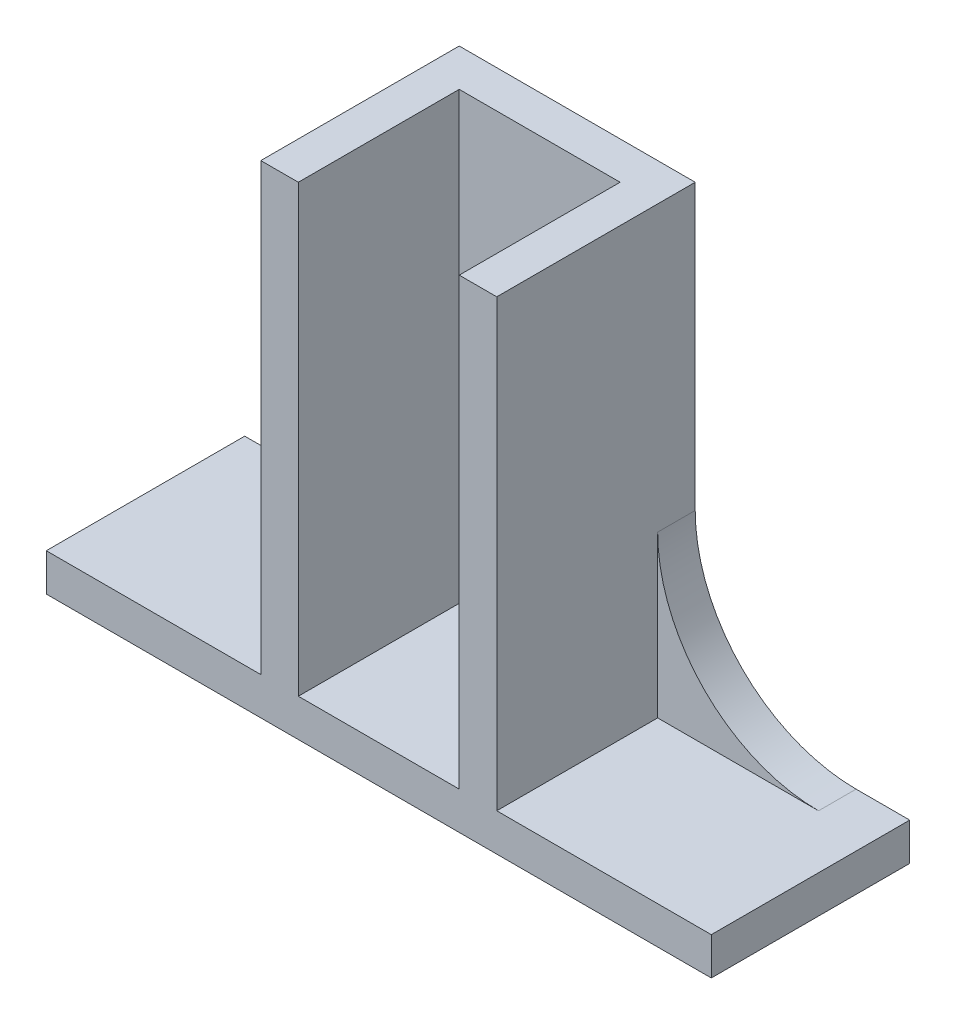
SolidWorks part; units mm, degrees
ref_plane "Front Plane" through (0, 0, 0) normal (0, 0, 1) x (1, 0, 0)
ref_plane "Top Plane" through (0, 0, 0) normal (0, 1, 0) x (1, 0, 0)
ref_plane "Right Plane" through (0, 0, 0) normal (1, 0, 0) x (0, 0, -1)
sketch "Sketch1" plane through (0, 0, 0) normal (0, 0, 1) x (1, 0, 0)
  line L1 (-16.1393, 44.8689) -> (5.8607, 44.8689)
  line L2 (-16.1393, 44.8689) -> (-16.1393, -0.1311)
  line L3 (-16.1393, -0.1311) -> (5.8607, -0.1311)
  line L4 (5.8607, 44.8689) -> (5.8607, -0.1311)
  dimension "D1" = 22
  dimension "D2" = 45
extrude "Boss-Extrude1" add sketch "Sketch1" along normal blind 18.5
sketch "Sketch2" plane through (0, 0, 18.5) normal (0, 0, 1) x (1, 0, 0)
  line L0 (5.8607, 44.8689) -> (-16.1393, 44.8689) construction
  line L1 (-12.6393, 44.8689) -> (2.3607, 44.8689)
  line L2 (-12.6393, 44.8689) -> (-12.6393, 3.3689)
  line L3 (-12.6393, 3.3689) -> (2.3607, 3.3689)
  line L4 (2.3607, 44.8689) -> (2.3607, 3.3689)
  line L5 (5.8607, -0.1311) -> (5.8607, 44.8689) construction
  line L6 (-16.1393, -0.1311) -> (5.8607, -0.1311) construction
  dimension "D1" = 15
  dimension "D2" = 3.5
  dimension "D3" = 3.5
extrude "Cut-Extrude1" cut sketch "Sketch2" against normal blind 15
sketch "Sketch3" plane through (0, 0, 0) normal (0, 0, -1) x (-1, 0, 0)
  line L1 (16.1393, -0.1311) -> (36.1393, -0.1311)
  line L2 (16.1393, -0.1311) -> (16.1393, 3.3689)
  line L3 (16.1393, 3.3689) -> (36.1393, 3.3689)
  line L4 (36.1393, -0.1311) -> (36.1393, 3.3689)
  line L5 (-5.8607, -0.1311) -> (-25.8607, -0.1311)
  line L6 (-5.8607, -0.1311) -> (-5.8607, 3.3689)
  line L7 (-5.8607, 3.3689) -> (-25.8607, 3.3689)
  line L8 (-25.8607, -0.1311) -> (-25.8607, 3.3689)
  dimension "D1" = 20
  dimension "D2" = 20
  dimension "D3" = 3.5
  dimension "D4" = 3.5
extrude "Boss-Extrude2" add sketch "Sketch3" against normal up to surface (18.5 mm away) up to face at (-5.1393, 23.2439, 18.5)
sketch "Sketch4" plane through (0, 0, 0) normal (0, 0, -1) x (-1, 0, 0)
  line L0 (31.1393, 3.3689) -> (16.1393, 3.3689)
  line L1 (36.1393, 3.3689) -> (16.1393, 3.3689) construction
  line L2 (16.1393, 3.3689) -> (16.1393, 18.3689)
  line L3 (16.1393, 44.8689) -> (16.1393, 3.3689) construction
  line L4 (-20.8607, 3.3689) -> (-5.8607, 3.3689)
  line L5 (-5.8607, 3.3689) -> (-25.8607, 3.3689) construction
  line L6 (-5.8607, 3.3689) -> (-5.8607, 18.3689)
  line L7 (-5.8607, 3.3689) -> (-5.8607, 44.8689) construction
  arc A0 (16.1393, 18.3689) -> (31.1393, 3.3689) centre (31.1393, 18.3689) ccw
  arc A1 (-5.8607, 18.3689) -> (-20.8607, 3.3689) centre (-20.8607, 18.3689) cw
  dimension "D1" = 15
extrude "Boss-Extrude3" add sketch "Sketch4" against normal blind 3.5
